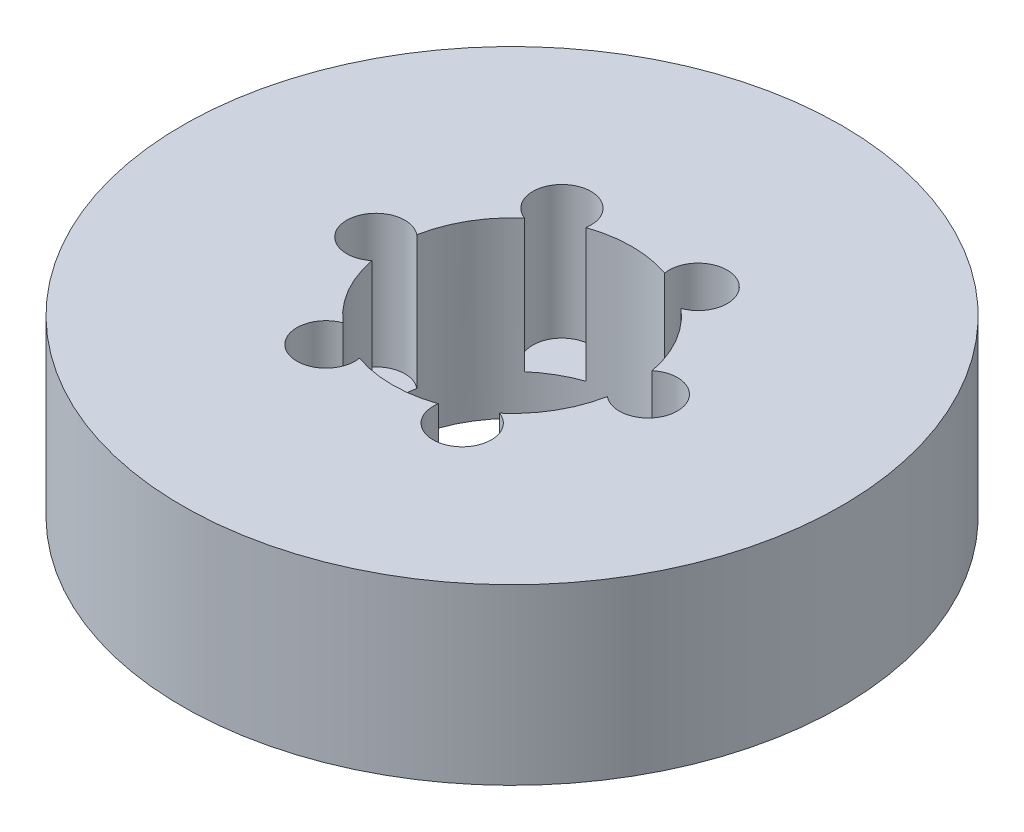
SolidWorks part; units mm, degrees
ref_plane "Front Plane" through (0, 0, 0) normal (0, 0, 1) x (1, 0, 0)
ref_plane "Top Plane" through (0, 0, 0) normal (0, 1, 0) x (1, 0, 0)
ref_plane "Right Plane" through (0, 0, 0) normal (1, 0, 0) x (0, 0, -1)
sketch "Sketch1" plane through (0, 0, 0) normal (0, 1, 0) x (1, 0, 0)
  circle A0 centre (0, 0) radius 55
  dimension "FLANGE_OD" = 110
extrude "Boss-Extrude1" add sketch "Sketch1" along normal blind 29
sketch "Sketch2" plane through (0, 0, 0) normal (0, 1, 0) x (1, 0, 0)
  circle A0 centre (0, 0) radius 20
  dimension "BORE_D" = 40
extrude "Cut-Extrude1" cut sketch "Sketch2" along normal through all
sketch "Sketch3" plane through (0, 29, 0) normal (0, 1, 0) x (1, 0, 0)
  circle A0 centre (0, 0) radius 22.7338 construction
  circle A1 centre (-22.7338, 0) radius 4.8569
  dimension "BOLT_D" = 9.7138
  dimension "BOLT_PCD" = 45.4677
extrude "Cut-Extrude2" cut sketch "Sketch3" against normal blind 22.2095
pattern_circular "CirPattern1" count 6 over 360 about axis through (0, 0, 0) along (0, 1, 0) of "Cut-Extrude2"
